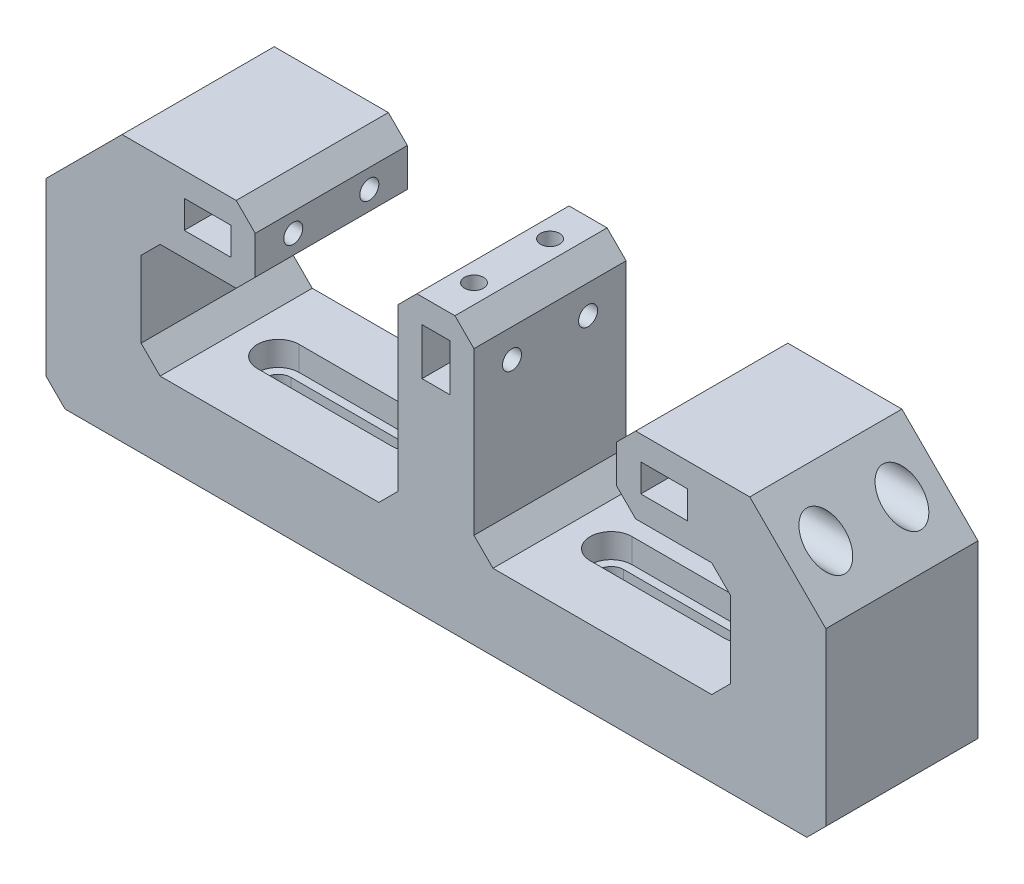
SolidWorks part; units mm, degrees
ref_plane "前基準面" through (0, 0, 0) normal (0, 0, 1) x (1, 0, 0)
ref_plane "上基準面" through (0, 0, 0) normal (0, 1, 0) x (1, 0, 0)
ref_plane "右基準面" through (0, 0, 0) normal (1, 0, 0) x (0, 0, -1)
sketch "草圖1" plane through (0, 0, 0) normal (0, 0, 1) x (1, 0, 0)
  line L0 (-82.5, 10) -> (-47.5, 10)
  line L1 (-47.5, 10) -> (-47.5, -10)
  line L2 (-47.5, -10) -> (-77.5, -10)
  line L3 (-77.5, -10) -> (-77.5, -40)
  line L4 (-77.5, -40) -> (-10, -40)
  line L5 (-10, 12.5) -> (-10, -40)
  line L6 (-10, 12.5) -> (10, 12.5)
  line L7 (10, 12.5) -> (10, -40)
  line L8 (10, -40) -> (77.5, -40)
  line L9 (77.5, -40) -> (77.5, -10)
  line L10 (77.5, -10) -> (47.5, -10)
  line L11 (47.5, -10) -> (47.5, 10)
  line L12 (47.5, 10) -> (82.5, 10)
  line L13 (102.5, -10) -> (102.5, -60)
  line L14 (102.5, -60) -> (-102.5, -60)
  line L15 (-102.5, -60) -> (-102.5, -10)
  line L16 (0, 0) -> (0, -64.1708) construction
  line L17 (53.85, 3.65) -> (53.85, -3.65)
  line L18 (-66.15, 3.65) -> (-53.85, 3.65)
  line L19 (-66.15, 3.65) -> (-66.15, -3.65)
  line L20 (-66.15, -3.65) -> (-53.85, -3.65)
  line L21 (-53.85, 3.65) -> (-53.85, -3.65)
  line L22 (66.15, -3.65) -> (53.85, -3.65)
  line L23 (66.15, 3.65) -> (66.15, -3.65)
  line L24 (66.15, 3.65) -> (53.85, 3.65)
  line L25 (-47.5, 0) -> (-102.5, 0) construction
  line L26 (3.65, 0) -> (-3.65, 0) construction
  line L27 (-3.65, 6.15) -> (3.65, 6.15)
  line L28 (-3.65, 6.15) -> (-3.65, -6.15)
  line L29 (-3.65, -6.15) -> (3.65, -6.15)
  line L30 (3.65, 6.15) -> (3.65, -6.15)
  line L31 (-53.85, 3.65) -> (-53.85, 10) construction
  line L32 (-53.85, 3.65) -> (-47.5, 3.65) construction
  line L33 (-3.65, 6.15) -> (-3.65, 12.5) construction
  line L34 (-60, -0.608) -> (-60, -7.908) construction
  line L35 (-102.5, -10) -> (-82.5, 10)
  line L36 (82.5, 10) -> (102.5, -10)
  point P0 (-102.5, 10)
  point P15 (102.5, 10)
  point P30 (-53.85, 0)
  point P35 (0, 6.15)
  point P36 (3.65, 0)
  point P38 (-60, 3.65)
  point P47 (-60, -3.65)
  point P48 (0, 0)
  dimension "D1" = 20
  dimension "D2" = 7.3
  dimension "D3" = 12.3
  dimension "D4" = 60
  dimension "D5" = 30
  dimension "D6" = 70
  dimension "D7" = 30
  dimension "D8" = 25
extrude "填料-伸長1" add sketch "草圖1" along normal blind 40
chamfer "導角1" distance 5 angle 45 6 edges at (47.5, -10, 20) (47.5, 10, 20) (10, 12.5, 20) (-10, 12.5, 20) (-47.5, -10, 20) (-47.5, 10, 20)
chamfer "導角2" distance 5 angle 45 6 edges at (-10, -40, 20) (10, -40, 20) (77.5, -40, 20) (-77.5, -40, 20) (-77.5, -10, 20) (77.5, -10, 20)
chamfer "導角3" distance 5 angle 45 2 edges at (-102.5, -60, 20) (102.5, -60, 20)
ref_plane "x 對稱面" through (0, 0, 0) normal (-1, 0, 0) x (0, 0, 1)
ref_plane "軌道水平面" through (0, 0, 0) normal (0, 1, 0) x (1, 0, 0)
ref_plane "z 對稱面" through (0, 0, 20) normal (0, 0, -1) x (-1, 0, 0)
ref_plane "軌道螺絲孔鑽孔起始面" through (102.5, 0, 0) normal (1, 0, 0) x (0, 0, -1)
ref_plane "軌道螺絲安裝面" through (0, 0, 10) normal (0, 0, -1) x (-1, 0, 0)
ref_plane "底面" through (0, -60, 0) normal (0, -1, 0) x (-1, 0, 0)
ref_plane "側軌道行進面" through (60, 0, 0) normal (-1, 0, 0) x (0, 0, 1)
ref_plane "底安裝孔上側面" through (0, -40, 0) normal (0, 1, 0) x (1, 0, 0)
ref_plane "偷挖材料用的面" through (0, -15, 0) normal (0, 1, 0) x (1, 0, 0)
sketch "草圖25" plane through (0, -60, 0) normal (0, -1, 0) x (-1, 0, 0)
  line L0 (96.5292, -10) -> (-96.5292, -10) construction
  line L1 (0, -22) -> (0, 22) construction
  circle A0 centre (0, -10) radius 5
  dimension "D1" = 10
extrude "底螺絲藏頭孔" cut sketch "草圖25" against normal blind 15
sketch "草圖26" plane through (0, -60, 0) normal (0, -1, 0) x (-1, 0, 0)
  circle A0 centre (0, -10) radius 2.5
  dimension "D1" = 5
extrude "底螺絲攻牙孔" cut sketch "草圖26" against normal through all contours A0
mirror "鏡射_另一排軌道的底孔" about plane through (0, 0, 20) normal (0, 0, -1) of "底螺絲攻牙孔", "底螺絲藏頭孔"
sketch "草圖23" plane through (102.5, 0, 0) normal (1, 0, 0) x (0, 0, -1)
  line L0 (-10, -96.5292) -> (-10, 96.5292) construction
  line L1 (37.2933, 0) -> (-37.2933, 0) construction
  circle A0 centre (-10, 0) radius 5
  dimension "D1" = 10
extrude "除料_左側螺絲藏頭孔" cut sketch "草圖23" against normal blind 25
sketch "草圖24" plane through (102.5, 0, 0) normal (1, 0, 0) x (0, 0, -1)
  circle A0 centre (-10, 0) radius 2.5
  dimension "D1" = 5
extrude "除料_左側螺絲攻牙孔" cut sketch "草圖24" against normal up to surface (98.85 mm away) contours A0 up to face at (3.65, 0, 20)
mirror "鏡射_右側孔" about plane through (0, 0, 0) normal (-1, 0, 0) of "除料_左側螺絲攻牙孔", "除料_左側螺絲藏頭孔"
mirror "鏡射_另一排軌道的安裝孔" about plane through (0, 0, 20) normal (0, 0, -1) of "鏡射_右側孔", "除料_左側螺絲攻牙孔", "除料_左側螺絲藏頭孔"
hole_wizard "M6 六角承窩頭蓋螺釘的柱孔2" positions "草圖38" profile "草圖37" size "M6" standard "ISO" slot yes end condition through all
sketch "草圖38" plane through (0, -40, 0) normal (0, 1, 0) x (1, 0, 0)
  line L0 (22.75, -20) -> (64.75, -20) construction
  line L1 (72.5, -20) -> (15, -20) construction
  line L2 (72.5, -40) -> (72.5, 0) construction
  line L3 (15, 0) -> (15, -40) construction
  point P0 (43.75, -20)
  dimension "D1" = 42
sketch "草圖37" plane through (43.75, -40, 20) normal (1, 0, 0) x (0, 0, 1)
  line L0 (0, 0) -> (0, 20)
  line L1 (0, 20) -> (3.3, 20)
  line L3 (3.3, 20) -> (3.3, 6.4)
  line L4 (3.3, 6.4) -> (5.5, 6.4)
  line L5 (5.5, 6.4) -> (5.5, 0)
  line L7 (5.5, 0) -> (0, 0)
  line L11 (0, -6.35) -> (0, 107.95) construction
  dimension "貫穿孔直徑" = 6.6
  dimension "貫穿孔深度" = 20
  dimension "柱孔直徑" = 11
  dimension "柱孔深度" = 6.4
mirror "另一側" about plane through (0, 0, 0) normal (-1, 0, 0) of "M6 六角承窩頭蓋螺釘的柱孔2"
